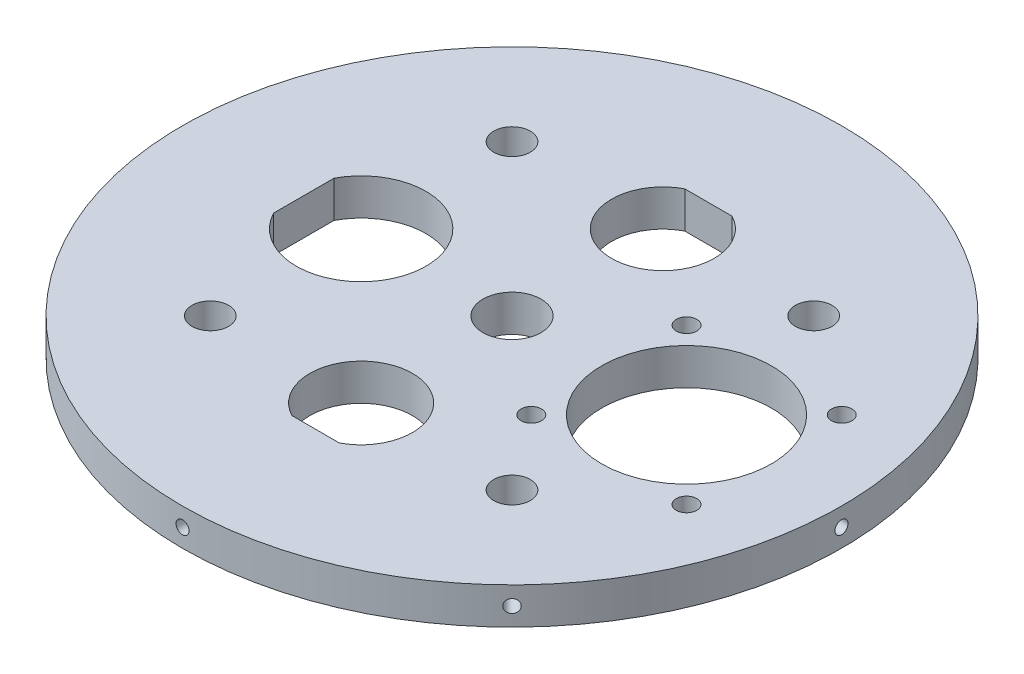
SolidWorks part; units mm, degrees
ref_plane "Front Plane" through (0, 0, 0) normal (0, 0, 1) x (1, 0, 0)
ref_plane "Top Plane" through (0, 0, 0) normal (0, 1, 0) x (1, 0, 0)
ref_plane "Right Plane" through (0, 0, 0) normal (1, 0, 0) x (0, 0, -1)
sketch "Sketch2" plane through (0, 0, 0) normal (0, 1, 0) x (1, 0, 0)
  circle A0 centre (0, 0) radius 57.15
  dimension "D1" = 114.3
extrude "Boss-Extrude1" add sketch "Sketch2" along normal blind 6.35 contours A0
sketch "Sketch6" plane through (0, 6.35, 0) normal (0, 1, 0) x (1, 0, 0)
  circle A0 centre (-26.1629, -26.1629) radius 3.175
  circle A1 centre (26.1629, -26.1629) radius 3.175
  circle A2 centre (-26.1629, 26.1631) radius 3.175
  circle A3 centre (26.1629, 26.1631) radius 3.175
  dimension "D1" = 6.35
  dimension "D2" = 74
  dimension "D3" = 26.1629
  dimension "D4" = 26.1629
  dimension "D5" = 26.1629
extrude "Cut-Extrude1" cut sketch "Sketch6" against normal up to next
sketch "Sketch7" plane through (0, 6.35, 0) normal (0, 1, 0) x (1, 0, 0)
  circle A0 centre (30, 0.2699) radius 14.732
  circle A3 centre (16.54, -13.1941) radius 1.778
  circle A4 centre (16.54, 13.7299) radius 1.778
  circle A5 centre (43.46, 13.7299) radius 1.778
  circle A6 centre (43.46, -13.1941) radius 1.778
  dimension "D1" = 29.464
  dimension "D2" = 3.556
  dimension "D3" = 3.556
  dimension "D4" = 3.556
  dimension "D5" = 3.556
  dimension "D6" = 13.46
  dimension "D7" = 13.46
  dimension "D8" = 13.46
  dimension "D9" = 13.464
  dimension "D10" = 30
extrude "Cut-Extrude2" cut sketch "Sketch7" against normal through all
sketch "Sketch8" plane through (0, 6.35, 0) normal (0, 1, 0) x (1, 0, 0)
  line L0 (4.0988, 34.0631) -> (-4.0988, 34.0631)
  line L1 (4.0988, -34.0629) -> (-4.0988, -34.0629)
  line L2 (-36.1129, 5.2498) -> (-36.1129, -5.2498)
  arc A0 (4.0988, -34.0629) -> (-4.0988, -34.0629) centre (0, -26.1629) ccw
  arc A1 (-4.0988, 34.0631) -> (4.0988, 34.0631) centre (0, 26.1631) ccw
  circle A2 centre (0, 0) radius 5.042
  arc A3 (-36.1129, -5.2498) -> (-36.1129, 5.2498) centre (-26.1629, 0) ccw
  circle A4 centre (26.1629, -26.1629) radius 3.175 construction
  circle A5 centre (26.1629, 26.1631) radius 3.175 construction
  circle A6 centre (-26.1629, -26.1629) radius 3.175 construction
  dimension "D1" = 17.8
  dimension "D2" = 17.8
  dimension "D3" = 10.084
  dimension "D4" = 22.5
  dimension "D5" = 7.9
  dimension "D6" = 0
  dimension "D7" = 7.9
  dimension "D8" = 0
  dimension "D9" = 9.95
  dimension "D10" = 0
extrude "Cut-Extrude3" cut sketch "Sketch8" against normal through all
sketch "Sketch10" plane through (0, 6.35, 0) normal (0, 1, 0) x (1, 0, 0)
  circle A0 centre (-26.1629, 26.1631) radius 7.9375
  circle A1 centre (26.1631, 26.1629) radius 7.9375
  circle A2 centre (26.1629, -26.1631) radius 7.9375
  circle A3 centre (-26.1631, -26.1629) radius 7.9375
  point P11 (0, 0)
  dimension "D1" = 4
sketch "Sketch11" plane through (0, 6.35, 0) normal (0, 1, 0) x (1, 0, 0)
  circle A0 centre (0, 0) radius 10
ref_plane "Plane1" through (0, 0, -57.15) normal (0, 0, -1) x (-1, 0, 0)
sketch "Sketch12" plane through (0, 0, -57.15) normal (0, 0, -1) x (-1, 0, 0)
  line L0 (57.15, 0) -> (57.15, 6.35) construction
  point P0 (0, 3.175)
  point P1 (57.15, 3.175)
hole_wizard "#4-40 Tapped Hole2" positions "3DSketch7" profile "Sketch16" tap size "#4-40" standard "ANSI Inch"
sketch3d "3DSketch7"
  point P0 (0, 3.175, -57.15)
sketch "Sketch16" plane through (0, 3.175, -57.15) normal (1, 0, 0) x (0, 1, 0)
  line L0 (0, 0) -> (0, 10.6792)
  line L1 (0, 10.6792) -> (1.1303, 10)
  line L2 (1.1303, 10) -> (1.1303, 0)
  line L5 (1.1303, 0) -> (0, 0)
  line L10 (0, 10.6792) -> (-1.1303, 10) construction
  line L11 (0, -6.35) -> (0, 107.95) construction
  dimension "Tap Drill Dia." = 2.2606
  dimension "Tap Drill Depth" = 10
  dimension "Drill Angle" = 118
cosmetic thread "Hole Thread2" parameters "D1"=5.69, "D2"=2.8448
pattern_circular "CirPattern1" count 8 over 360 about axis through (0, 0, 0) along (0, 1, 0) of "#4-40 Tapped Hole2"
cosmetic thread "Hole Thread3" parameters "D1"=5.69, "D2"=2.8448
cosmetic thread "Hole Thread4" parameters "D1"=5.69, "D2"=2.8448
cosmetic thread "Hole Thread5" parameters "D1"=5.69, "D2"=2.8448
cosmetic thread "Hole Thread6" parameters "D1"=5.69, "D2"=2.8448
cosmetic thread "Hole Thread7" parameters "D1"=5.69, "D2"=2.8448
cosmetic thread "Hole Thread8" parameters "D1"=5.69, "D2"=2.8448
cosmetic thread "Hole Thread9" parameters "D1"=5.69, "D2"=2.8448
equation "\"width\"=26.1629"
equation "\"D4@Sketch6\"=\"width\""
equation "\"D3@Sketch6\"=\"width\""
equation "\"D5@Sketch6\"=\"width\""
